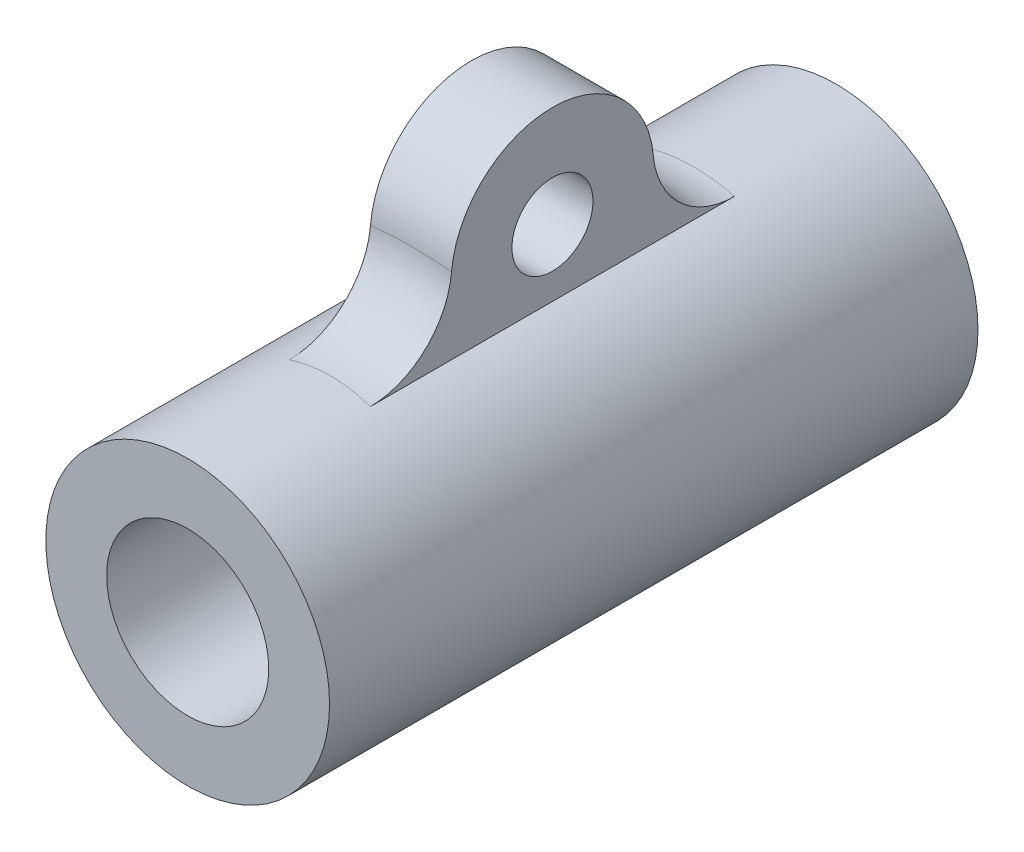
SolidWorks part; units mm, degrees
material "Plain Carbon Steel"
ref_plane "Front Plane" through (0, 0, 0) normal (0, 0, 1) x (1, 0, 0)
ref_plane "Top Plane" through (0, 0, 0) normal (0, 1, 0) x (1, 0, 0)
ref_plane "Right Plane" through (0, 0, 0) normal (1, 0, 0) x (0, 0, -1)
sketch "Sketch1" plane through (0, 0, 0) normal (0, 0, 1) x (1, 0, 0)
  circle A0 centre (0, 0) radius 6.35
  circle A1 centre (0, 0) radius 11.1125
  dimension "D1" = 12.7
  dimension "D2" = 4.7625
extrude "Boss-Extrude1" add sketch "Sketch1" along normal mid plane 50.8
sketch "Sketch2" plane through (0, 0, 0) normal (1, 0, 0) x (0, 0, -1)
  line L0 (0, 12.7) -> (0, 11.1125) construction
  line L1 (25.4, 11.1125) -> (-25.4, 11.1125) construction
  circle A2 centre (0, 15.875) radius 7.9375
  circle A3 centre (0, 15.875) radius 3.175
  point P0 (0, 0)
  point P2 (0, 12.0435)
  point P7 (0, 0)
  point P11 (0, 0)
  dimension "D1" = 6.35
  dimension "D3" = 4.7625
  dimension "D2" = 1.5875
extrude "Boss-Extrude3" add sketch "Sketch2" along normal mid plane 6.35 contours A3 A2 region at (0, 15.875, 7.713)
fillet "Fillet1" radius 6.35 2 edges at (-0.3252, 11.1077, 6.3464) (0.3252, 11.1077, -6.3464)
